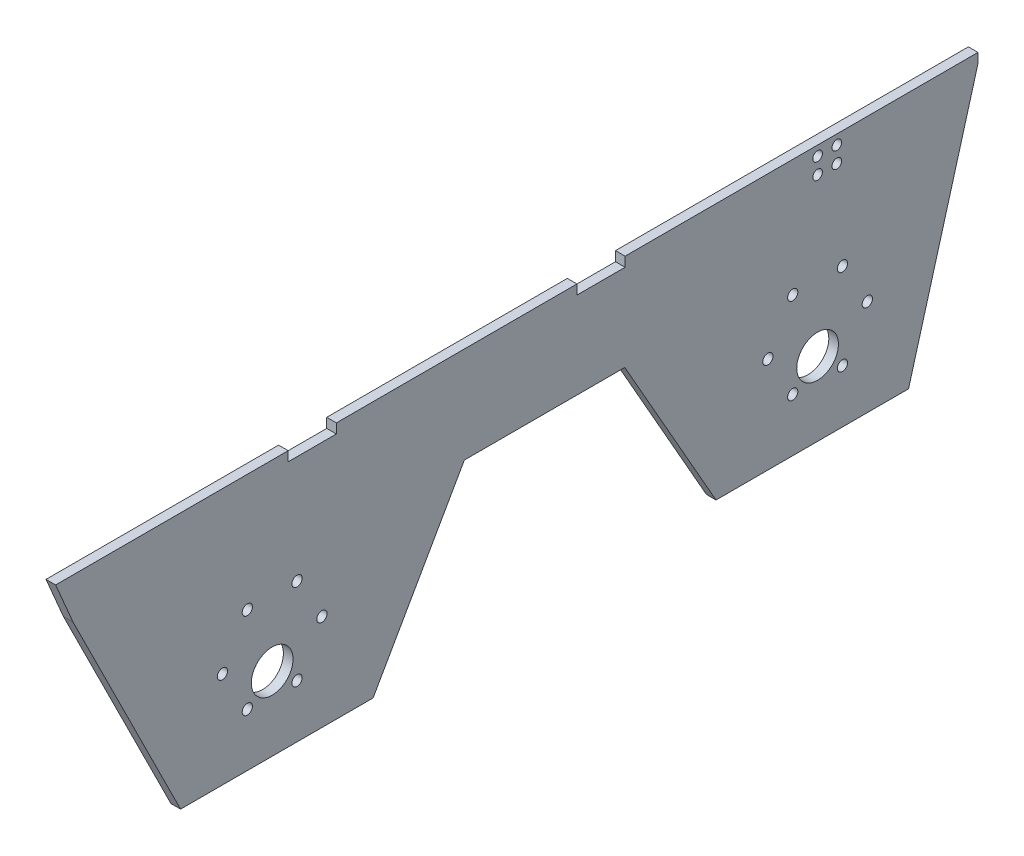
SolidWorks part; units mm, degrees
ref_plane "前视基准面" through (0, 0, 0) normal (0, 0, 1) x (1, 0, 0)
ref_plane "上视基准面" through (0, 0, 0) normal (0, 1, 0) x (1, 0, 0)
ref_plane "右视基准面" through (0, 0, 0) normal (1, 0, 0) x (0, 0, -1)
sketch "草图1" plane through (0, 0, 0) normal (0, 0, 1) x (1, 0, 0)
  line L0 (0, 4.1733) -> (0, -73.8267)
  line L1 (0, -73.8267) -> (3, -73.8267)
  line L2 (3, -73.8267) -> (3, 1.1733)
  line L3 (5, 3.1733) -> (80, 3.1733)
  line L4 (80, 3.1733) -> (80, 6.1733)
  line L5 (80, 6.1733) -> (2, 6.1733)
  line L6 (0, 4.1733) -> (0, 6.1733)
  line L7 (0, 6.1733) -> (2, 6.1733)
  line L8 (3, 1.1733) -> (3, 3.1733)
  line L9 (3, 3.1733) -> (5, 3.1733)
  dimension "D1" = 3
  dimension "D2" = 3
  dimension "D4" = 80
  dimension "D5" = 80
extrude "凸台-拉伸1" add sketch "草图1" along normal blind 150 and the other way blind 150
ref_plane "基准面4" through (0, 0, 20) normal (0, 0, -1) x (-1, 0, 0)
sketch "草图4" plane through (0, 6.1733, 0) normal (0, 1, 0) x (1, 0, 0)
  line L0 (80, -150) -> (0, -150) construction
  line L1 (21.5, -72.5) -> (11.5, -72.5) construction
  line L2 (21.5, -72.5) -> (21.5, -127.5) construction
  line L3 (21.5, -127.5) -> (11.5, -127.5) construction
  line L4 (11.5, -72.5) -> (11.5, -127.5) construction
  line L5 (21.5, -72.5) -> (11.5, -127.5) construction
  line L6 (21.5, -127.5) -> (11.5, -72.5) construction
  line L7 (0, 0) -> (293.52, 0) construction
  line L8 (21.5, 127.5) -> (11.5, 72.5) construction
  line L9 (21.5, 72.5) -> (11.5, 127.5) construction
  line L10 (11.5, 72.5) -> (11.5, 127.5) construction
  line L11 (21.5, 127.5) -> (11.5, 127.5) construction
  line L12 (21.5, 72.5) -> (21.5, 127.5) construction
  line L13 (21.5, 72.5) -> (11.5, 72.5) construction
  line L14 (148.5, 100) -> (148.5, -33.0451) construction
  line L15 (0, 150) -> (0, -150) construction
  circle A0 centre (11.5, -72.5) radius 2.5
  circle A3 centre (11.5, -127.5) radius 2.5
  circle A4 centre (11.5, 127.5) radius 2.5
  circle A5 centre (21.5, 127.5) radius 2.5
  circle A6 centre (21.5, 72.5) radius 2.5
  circle A7 centre (11.5, 72.5) radius 2.5
  point P9 (16.5, -100)
  point P21 (16.5, 100)
  dimension "D1" = 50
  dimension "D2" = 132
  dimension "D3" = 11.5
extrude "切除-拉伸4" cut sketch "草图4" against normal blind 3 contours A0 | A3 region at (11.5, 6.1733, 72.5) region at (11.5, 6.1733, 127.5)
sketch "草图5" plane through (0, 6.1733, 0) normal (0, 1, 0) x (1, 0, 0)
  line L0 (80, -150) -> (0, -150) construction
  line L1 (80, -150) -> (28, -150)
  line L2 (80, -150) -> (80, -50)
  line L3 (80, -50) -> (28, -50)
  line L4 (28, -150) -> (28, -50)
  line L5 (80, -150) -> (28, -50) construction
  line L6 (80, -50) -> (28, -150) construction
  point P4 (54, -100)
  dimension "D1" = 100
  dimension "D2" = 52
extrude "切除-拉伸5" cut sketch "草图5" against normal blind 3
sketch "草图6" plane through (0, 6.1733, 0) normal (0, 1, 0) x (1, 0, 0)
  line L0 (80, 150) -> (0, 150) construction
  line L1 (80, 150) -> (40, 150)
  line L2 (80, 150) -> (80, -50)
  line L3 (80, -50) -> (40, -50)
  line L4 (40, 150) -> (40, -50)
  line L5 (80, 150) -> (40, -50) construction
  line L6 (80, -50) -> (40, 150) construction
  line L7 (80, 150) -> (80, -50) construction
  point P4 (60, 50)
  dimension "D1" = 40
  dimension "D2" = 200
sketch "草图7" plane through (3, 0, 0) normal (1, 0, 0) x (0, 0, -1)
  line L0 (150, 6.1733) -> (150, -73.8267) construction
  line L5 (124.7487, -19.078) -> (124.7253, -19.1014) construction
  line L6 (124.7487, -68.5755) -> (124.7253, -68.552) construction
  line L7 (75.2747, -19.1014) -> (75.2513, -19.078) construction
  line L8 (75.2747, -68.552) -> (75.2513, -68.5755) construction
  line L9 (100, -43.8267) -> (-70, -43.8267) construction
  line L10 (-94.7487, -19.078) -> (-45.2513, -19.078) construction
  line L11 (-94.7487, -19.078) -> (-94.7487, -68.5755) construction
  line L12 (-94.7487, -68.5755) -> (-45.2513, -68.5755) construction
  line L13 (-45.2513, -19.078) -> (-45.2513, -68.5755) construction
  line L14 (-94.7487, -19.078) -> (-45.2513, -68.5755) construction
  line L15 (-94.7487, -68.5755) -> (-45.2513, -19.078) construction
  line L16 (75.2513, -19.078) -> (-45.2513, -19.078) construction
  line L17 (124.7487, -19.078) -> (75.2513, -19.078) construction
  line L18 (124.7487, -19.078) -> (124.7487, -68.5755) construction
  line L19 (124.7487, -68.5755) -> (75.2513, -68.5755) construction
  line L20 (75.2513, -19.078) -> (75.2513, -68.5755) construction
  line L21 (124.7487, -19.078) -> (75.2513, -68.5755) construction
  line L22 (124.7487, -68.5755) -> (75.2513, -19.078) construction
  line L23 (75.2513, -68.5755) -> (-45.2513, -68.5755) construction
  line L24 (-150, 6.1733) -> (-150, -73.8267) construction
  line L25 (-70, -43.8267) -> (-70, -50.8267) construction
  line L26 (100, -43.8267) -> (100, -50.8267) construction
  circle A8 centre (100, -43.8267) radius 34.9668 construction
  circle A9 centre (-70, -43.8267) radius 15.5 construction
  circle A10 centre (100, -43.8267) radius 15.5 construction
  circle A11 centre (84.5, -43.8267) radius 1.6
  circle A12 centre (92.25, -57.2501) radius 1.6
  circle A13 centre (107.75, -57.2501) radius 1.6
  circle A14 centre (115.5, -43.8267) radius 1.6
  circle A15 centre (107.75, -30.4033) radius 1.6
  circle A16 centre (92.25, -30.4033) radius 1.6
  circle A17 centre (-54.5, -43.8267) radius 1.6
  circle A18 centre (-62.25, -57.2501) radius 1.6
  circle A19 centre (-77.75, -57.2501) radius 1.6
  circle A20 centre (-85.5, -43.8267) radius 1.6
  circle A21 centre (-77.75, -30.4033) radius 1.6
  circle A22 centre (-62.25, -30.4033) radius 1.6
  circle A23 centre (-70, -50.8267) radius 6.5
  circle A24 centre (100, -50.8267) radius 6.5
  point P5 (-54.5, -43.8267)
  point P17 (100, -43.8267)
  point P28 (-70, -43.8267)
  point P30 (100, -43.8267)
  point P39 (100, -43.8267)
  point P53 (-70, -43.8267)
  dimension "D1" = 50
  dimension "D2" = 80
  dimension "D3" = 31
  dimension "D4" = 6
  dimension "D5" = 3.2
  dimension "D7" = 7
  dimension "D6" = 6
extrude "切除-拉伸9" cut sketch "草图7" against normal through all contours A11 | A11 | A12 | A13 | A17 | L12 A17 L13 | L12 A12 L11 | A9 | A8 | A10 | A13 | A20 | A21 | A19 | A18 | A22 | A16 | A14 | A15 | A23 | A24 region at (3, -43.8267, -84.5) region at (3, -57.2501, -92.25) region at (3, -57.2501, -107.75) region at (3, -43.8267, 54.5)
extrude "切除-拉伸10" cut sketch "草图6" against normal blind 10 contours L4 L3 L2 L1
ref_plane "基准面5" through (23.76, 6.1733, -141) normal (1, 0, 0) x (0, 0, -1)
sketch "草图11" plane through (0, 0, 0) normal (-1, 0, 0) x (0, 0, 1)
  line L1 (-150, -73.8267) -> (150, -73.8267) construction
  line L2 (-150, 6.1733) -> (-150, -73.8267) construction
  line L5 (-128.3451, -73.8267) -> (-150, -73.8267)
  line L6 (-150, -73.8267) -> (-150, 3.1733)
  line L7 (-150, 6.1733) -> (-150, -73.8267) construction
  line L8 (-150, 3.1733) -> (-128.3451, -73.8267)
  dimension "D1" = 77
extrude "切除-拉伸12" cut sketch "草图11" against normal blind 4
sketch "草图12" plane through (0, 6.1733, 0) normal (0, 1, 0) x (1, 0, 0)
  line L0 (40, 150) -> (40, -50) construction
  line L1 (40, 150) -> (6, 150)
  line L2 (40, 150) -> (40, 40)
  line L3 (40, 40) -> (6, 40)
  line L4 (6, 150) -> (6, 40)
  line L5 (40, 150) -> (6, 40) construction
  line L6 (40, 40) -> (6, 150) construction
  point P4 (23, 95)
  dimension "D1" = 110
  dimension "D2" = 34
extrude "切除-拉伸13" cut sketch "草图12" against normal blind 4
sketch "草图14" plane through (0, 3.1733, 0) normal (0, -1, 0) x (1, 0, 0)
  line L0 (3, -150) -> (3, 150) construction
  line L1 (7.2, -110) -> (3, -110)
  line L2 (7.2, -110) -> (7.2, -96)
  line L3 (7.2, -96) -> (3, -96)
  line L4 (3, -110) -> (3, -96)
  line L5 (7.2, -110) -> (3, -96) construction
  line L6 (7.2, -96) -> (3, -110) construction
  line L7 (3, -150) -> (6, -150) construction
  point P4 (5.1, -103)
  dimension "D1" = 4.2
  dimension "D2" = 40
  dimension "D3" = 4.2
  dimension "D4" = 14
extrude "切除-拉伸14" cut sketch "草图14" against normal blind 10
sketch "草图15" plane through (0, 6.1733, 0) normal (0, 1, 0) x (1, 0, 0)
  line L0 (40, -50) -> (40, 40) construction
  circle A0 centre (32, -4.5) radius 2
  circle A2 centre (11.5, -127.5) radius 2.5 construction
  dimension "D1" = 8
  dimension "D2" = 123
extrude "切除-拉伸15" cut sketch "草图15" against normal blind 26
sketch "草图17" plane through (0, 3.1733, 0) normal (0, -1, 0) x (1, 0, 0)
  line L0 (28, 50) -> (28, 150) construction
  line L1 (3, 150) -> (28, 150) construction
  circle A0 centre (23.6907, 113.5) radius 1.5
  dimension "D1" = 4.3093
  dimension "D2" = 36.5
extrude "切除-拉伸19" cut sketch "草图17" against normal blind 10
sketch "草图18" plane through (0, 0, 0) normal (-1, 0, 0) x (0, 0, 1)
  line L0 (150, -73.8267) -> (118.5501, -73.8267)
  line L1 (-128.3451, -73.8267) -> (150, -73.8267) construction
  line L2 (118.5501, -73.8267) -> (150, 0)
  line L3 (150, 6.1733) -> (150, -73.8267) construction
  line L4 (150, 0) -> (150, -73.8267)
extrude "切除-拉伸20" cut sketch "草图18" against normal blind 10
sketch "草图19" plane through (0, 6.1733, 0) normal (0, 1, 0) x (1, 0, 0)
  line L0 (3, 96) -> (6, 96) construction
  line L1 (3, 96) -> (4.2, 96)
  line L2 (3, 96) -> (3, 110)
  line L3 (3, 110) -> (4.2, 110)
  line L4 (4.2, 96) -> (4.2, 110)
  line L5 (3, 96) -> (4.2, 110) construction
  line L6 (3, 110) -> (4.2, 96) construction
  line L7 (3, 110) -> (3, 96) construction
  line L8 (6, 110) -> (3, 110) construction
  point P4 (3.6, 103)
sketch "草图21" plane through (0, 0, 0) normal (-1, 0, 0) x (0, 0, 1)
  line L11 (118.5501, -73.8267) -> (150, 0)
  line L12 (150, 0) -> (118.5501, -73.8267) construction
  line L13 (150, 0) -> (150, 6.1733)
  line L14 (-150, 6.1733) -> (150, 6.1733) construction
  line L15 (150, 6.1733) -> (137.5, 6.1733)
  line L16 (137.5, 6.1733) -> (132.0722, -6.5682)
  line L21 (98.5501, -73.8267) -> (118.5501, -73.8267)
  line L22 (98.5501, -73.8267) -> (132.0722, -6.5682)
  dimension "D1" = 20
  dimension "D3" = 12.5
extrude "切除-拉伸21" cut sketch "草图21" against normal blind 31
sketch "草图22" plane through (0, 0, 0) normal (-1, 0, 0) x (0, 0, 1)
  line L0 (-150, 6.1733) -> (-150, 3.1733) construction
  line L1 (-150, 6.1733) -> (137.5, 6.1733) construction
  circle A0 centre (-106, 3.1733) radius 1.5
  circle A3 centre (-100, 3.1733) radius 1.5
  circle A5 centre (-106, -1.8267) radius 1.5
  circle A7 centre (-100, -1.8267) radius 1.5
  circle A10 centre (-106, -6.8267) radius 1.5 [skipped]
  circle A11 centre (-100, -6.8267) radius 1.5 [skipped]
  dimension "D1" = 44
  dimension "D2" = 6
  dimension "D3" = 3
  dimension "D4" = 5
  dimension "D5" = 3
  dimension "D8" = 3
  dimension "D10" = 3
extrude "切除-拉伸22" cut sketch "草图22" against normal blind 31
sketch "草图23" plane through (0, 6.1733, 0) normal (0, 1, 0) x (1, 0, 0)
  line L0 (40, -50) -> (28, -50) construction
  line L1 (28, -50) -> (40, -50)
  line L2 (28, -50) -> (28, -137.5)
  line L3 (28, -137.5) -> (40, -137.5)
  line L4 (40, -50) -> (40, -137.5)
  line L5 (28, -50) -> (40, -137.5) construction
  line L6 (28, -137.5) -> (40, -50) construction
  point P4 (34, -93.75)
  dimension "D1" = 12
extrude "凸台-拉伸3" add sketch "草图23" against normal blind 3
sketch "草图24" plane through (28, 0, 0) normal (-1, 0, 0) x (0, 0, 1)
  line L0 (137.5, 6.1733) -> (137.5, 3.1733)
  line L1 (137.5, 3.1733) -> (137.5, 6.1733) construction
  line L2 (137.5, 6.1733) -> (136.222, 3.1733) construction
  line L3 (137.5, 3.1733) -> (136.222, 3.1733)
  line L4 (136.222, 3.1733) -> (137.5, 6.1733)
extrude "切除-拉伸23" cut sketch "草图24" against normal blind 18
sketch "草图25" plane through (0, 6.1733, 0) normal (0, 1, 0) x (1, 0, 0)
  circle A0 centre (32, -61) radius 1.5
  dimension "D1" = 3
extrude "切除-拉伸24" cut sketch "草图25" against normal blind 4 and the other way blind 13
sketch "草图26" plane through (0, 3.1733, 0) normal (0, -1, 0) x (1, 0, 0)
  line L0 (32, -25.5) -> (32, 4.5) construction
  circle A0 centre (32, -25.5) radius 2
  circle A1 centre (32, 4.5) radius 2 construction
  dimension "D1" = 30
extrude "切除-拉伸25" cut sketch "草图26" against normal blind 10
sketch "草图27" plane through (0, 3.1733, 0) normal (0, -1, 0) x (1, 0, 0)
  circle A0 centre (23.6907, 123.5) radius 1.5
extrude "切除-拉伸26" cut sketch "草图27" against normal blind 10
sketch "草图16" plane through (0, 3.1733, 0) normal (0, -1, 0) x (1, 0, 0)
  circle A0 centre (17.5, 137.5) radius 1.5
sketch "草图30" plane through (0, 6.1733, 0) normal (0, 1, 0) x (1, 0, 0)
  circle A0 centre (11.5, -119) radius 1.5
sketch "草图31" plane through (3, 0, 0) normal (1, 0, 0) x (0, 0, -1)
  line L0 (-38.5501, -73.8267) -> (-10.1025, -23.8267)
  line L1 (128.3451, -73.8267) -> (-98.5501, -73.8267) construction
  line L2 (-10.1025, -23.8267) -> (39.8975, -23.8267)
  line L3 (39.8975, -23.8267) -> (68.3451, -73.8267)
  line L4 (68.3451, -73.8267) -> (-38.5501, -73.8267)
  dimension "D1" = 60
  dimension "D2" = 60
  dimension "D3" = 50
  dimension "D4" = 50
extrude "切除-拉伸29" cut sketch "草图31" against normal blind 10
sketch "草图32" plane through (0, 0, -150) normal (0, 0, -1) x (-1, 0, 0)
  line L1 (-3, 3.1733) -> (-47.6285, 3.1733)
  line L2 (-3, 3.1733) -> (-3, 11.186)
  line L3 (-3, 11.186) -> (-47.6285, 11.186)
  line L4 (-47.6285, 3.1733) -> (-47.6285, 11.186)
  line L5 (-3, 3.1733) -> (-47.6285, 11.186) construction
  line L6 (-3, 11.186) -> (-47.6285, 3.1733) construction
  point P4 (-25.3142, 7.1796)
extrude "切除-拉伸30" cut sketch "草图32" against normal blind 345
sketch "草图33" plane through (0, 6.1733, 0) normal (0, 1, 0) x (1, 0, 0)
  line L0 (3, 150) -> (3, -137.5) construction
  line L1 (3, 40) -> (0, 40)
  line L2 (3, 40) -> (3, 25)
  line L3 (3, 25) -> (0, 25)
  line L4 (0, 40) -> (0, 25)
  line L5 (3, 40) -> (0, 25) construction
  line L6 (3, 25) -> (0, 40) construction
  line L7 (0, 150) -> (0, -137.5) construction
  line L9 (3, -65) -> (0, -65)
  line L10 (3, -65) -> (3, -50)
  line L11 (3, -50) -> (0, -50)
  line L12 (0, -65) -> (0, -50)
  line L13 (3, -65) -> (0, -50) construction
  line L14 (3, -50) -> (0, -65) construction
  point P4 (1.5, 32.5)
  point P13 (1.5, -57.5)
extrude "切除-拉伸31" cut sketch "草图33" against normal blind 3
